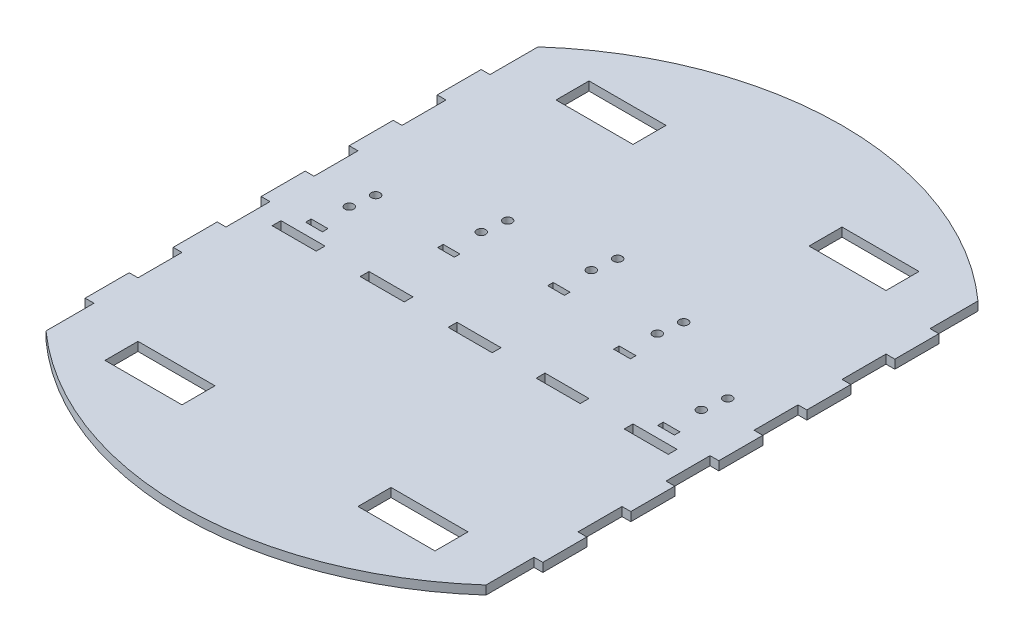
SolidWorks part; units mm, degrees
ref_plane "Přední rovina" through (0, 0, 0) normal (0, 0, 1) x (1, 0, 0)
ref_plane "Horní rovina" through (0, 0, 0) normal (0, 1, 0) x (1, 0, 0)
ref_plane "Pravá rovina" through (0, 0, 0) normal (1, 0, 0) x (0, 0, -1)
sketch "Skica1" plane through (0, 0, 0) normal (0, 1, 0) x (1, 0, 0)
  line L0 (-150, 0) -> (150, 0)
  line L5 (-200, 111.8034) -> (-100, 111.8034)
  line L6 (-200, 111.8034) -> (-200, -111.8034)
  line L7 (-200, -111.8034) -> (-100, -111.8034)
  line L8 (-100, 111.8034) -> (-100, -111.8034)
  line L9 (-200, 111.8034) -> (-100, -111.8034) construction
  line L10 (-200, -111.8034) -> (-100, 111.8034) construction
  line L15 (200, -111.8034) -> (100, -111.8034)
  line L16 (100, 111.8034) -> (100, -111.8034)
  line L17 (-100, -90) -> (-104, -90)
  line L18 (-100, -90) -> (-100, -70)
  line L19 (-100, -70) -> (-104, -70)
  line L20 (-104, -90) -> (-104, -70)
  line L21 (-100, -50) -> (-104, -50)
  line L22 (-100, -50) -> (-100, -30)
  line L23 (-100, -30) -> (-104, -30)
  line L24 (-104, -50) -> (-104, -30)
  line L25 (0, -150) -> (0, 150)
  line L26 (-100, 30) -> (-104, 30)
  line L27 (-104, 50) -> (-104, 30)
  line L28 (-100, 50) -> (-104, 50)
  line L29 (-100, 50) -> (-100, 30)
  line L30 (-100, 70) -> (-104, 70)
  line L31 (-104, 90) -> (-104, 70)
  line L32 (-100, 90) -> (-104, 90)
  line L33 (-100, 90) -> (-100, 70)
  line L34 (200, 111.8034) -> (100, 111.8034)
  line L35 (200, 111.8034) -> (200, -111.8034)
  line L36 (100, 90) -> (100, 70)
  line L37 (100, 90) -> (104, 90)
  line L38 (104, 90) -> (104, 70)
  line L39 (100, 70) -> (104, 70)
  line L40 (100, 50) -> (100, 30)
  line L41 (100, 50) -> (104, 50)
  line L42 (104, 50) -> (104, 30)
  line L43 (100, 30) -> (104, 30)
  line L44 (100, -30) -> (104, -30)
  line L45 (104, -50) -> (104, -30)
  line L46 (100, -50) -> (104, -50)
  line L47 (100, -50) -> (100, -30)
  line L48 (100, -70) -> (104, -70)
  line L49 (104, -90) -> (104, -70)
  line L50 (100, -90) -> (104, -90)
  line L51 (100, -90) -> (100, -70)
  line L52 (-3.81, 22.54) -> (3.81, 22.54)
  line L53 (-83.81, -10) -> (-76.19, -10)
  line L54 (-83.81, -10) -> (-83.81, -7.46)
  line L55 (-83.81, -7.46) -> (-76.19, -7.46)
  line L56 (-76.19, -10) -> (-76.19, -7.46)
  line L57 (-3.81, 22.54) -> (-3.81, 20)
  line L58 (-3.81, 20) -> (3.81, 20)
  line L59 (3.81, 22.54) -> (3.81, 20)
  line L60 (-43.81, 10) -> (-36.19, 10)
  line L61 (-43.81, 10) -> (-43.81, 12.54)
  line L62 (-43.81, 12.54) -> (-36.19, 12.54)
  line L63 (-36.19, 10) -> (-36.19, 12.54)
  line L64 (43.81, 10) -> (43.81, 12.54)
  line L65 (43.81, 12.54) -> (36.19, 12.54)
  line L66 (36.19, 10) -> (36.19, 12.54)
  line L67 (43.81, 10) -> (36.19, 10)
  line L68 (83.81, -7.46) -> (76.19, -7.46)
  line L69 (76.19, -10) -> (76.19, -7.46)
  line L70 (83.81, -10) -> (76.19, -10)
  line L71 (83.81, -10) -> (83.81, -7.46)
  line L72 (100, 10) -> (104, 10)
  line L73 (-100, -10) -> (-104, -10)
  line L74 (-100, -10) -> (-100, 10)
  line L75 (-100, 10) -> (-104, 10)
  line L76 (-104, -10) -> (-104, 10)
  line L77 (104, -10) -> (104, 10)
  line L78 (100, -10) -> (104, -10)
  line L79 (100, -10) -> (100, 10)
  line L80 (-40, 12.54) -> (-40, 26.04)
  line L81 (-80, -7.46) -> (-80, 6.04)
  line L82 (40, 12.54) -> (40, 26.04)
  line L83 (80, -7.46) -> (80, 6.04)
  line L84 (-100, -15) -> (100, -15)
  line L85 (50, -19) -> (30, -19)
  line L86 (-90, -15) -> (-70, -15)
  line L87 (-90, -15) -> (-90, -19)
  line L88 (-90, -19) -> (-70, -19)
  line L89 (-70, -15) -> (-70, -19)
  line L90 (-50, -15) -> (-30, -15)
  line L91 (-50, -15) -> (-50, -19)
  line L92 (-50, -19) -> (-30, -19)
  line L93 (-30, -15) -> (-30, -19)
  line L94 (-10, -15) -> (10, -15)
  line L95 (-10, -15) -> (-10, -19)
  line L96 (-10, -19) -> (10, -19)
  line L97 (10, -15) -> (10, -19)
  line L98 (30, -15) -> (30, -19)
  line L99 (50, -15) -> (30, -15)
  line L100 (50, -15) -> (50, -19)
  line L101 (90, -19) -> (70, -19)
  line L102 (70, -15) -> (70, -19)
  line L103 (90, -15) -> (70, -15)
  line L104 (90, -15) -> (90, -19)
  line L105 (75, -95) -> (40, -95)
  line L106 (40, -110) -> (40, -95)
  line L107 (-75, -110) -> (-40, -110)
  line L108 (-75, -110) -> (-75, -95)
  line L109 (-75, -95) -> (-40, -95)
  line L110 (-40, -110) -> (-40, -95)
  line L111 (75, -110) -> (40, -110)
  line L112 (75, -110) -> (75, -95)
  line L113 (-75, 95) -> (-40, 95)
  line L114 (-40, 110) -> (-40, 95)
  line L115 (-75, 110) -> (-40, 110)
  line L116 (-75, 110) -> (-75, 95)
  line L117 (75, 110) -> (75, 95)
  line L118 (75, 110) -> (40, 110)
  line L119 (40, 110) -> (40, 95)
  line L120 (75, 95) -> (40, 95)
  circle A0 centre (0, 0) radius 150
  circle A1 centre (0, 36.04) radius 2
  circle A2 centre (1.5, 46.54) radius 2
  circle A3 centre (80, 6.04) radius 2
  circle A4 centre (40, 26.04) radius 2
  circle A5 centre (41.5, 36.54) radius 2
  circle A6 centre (81.5, 16.54) radius 2
  circle A7 centre (-40, 26.04) radius 2
  circle A8 centre (-38.5, 36.54) radius 2
  circle A9 centre (-80, 6.04) radius 2
  circle A10 centre (-78.5, 16.54) radius 2
  point P2 (-150, 0)
  point P8 (150, 0)
  point P17 (-102, -90)
  point P50 (-76.19, -8.73)
  point P64 (-80, -7.46)
  point P71 (-40, 12.54)
  dimension "D1" = 300
  dimension "D26" = 4
  dimension "D28" = 4
  dimension "D31" = 4
  dimension "D32" = 4
  dimension "D35" = 4
  dimension "D36" = 4
  dimension "D37" = 4
  dimension "D38" = 4
  dimension "D39" = 4
  dimension "D40" = 4
  dimension "D3" = 4
  dimension "D4" = 20
  dimension "D5" = 20
  dimension "D6" = 4
  dimension "D7" = 20
  dimension "D8" = 30
  dimension "D9" = 2.54
  dimension "D10" = 7.62
  dimension "D11" = 7.62
  dimension "D12" = 2.54
  dimension "D13" = 3.81
  dimension "D14" = 80
  dimension "D15" = 7.62
  dimension "D16" = 2.54
  dimension "D17" = 40
  dimension "D18" = 20
  dimension "D19" = 10
  dimension "D20" = 10
  dimension "D21" = 10
  dimension "D22" = 20
  dimension "D23" = 4
  dimension "D24" = 50
  dimension "D25" = 90
  dimension "D27" = 13.5
  dimension "D29" = 24
  dimension "D30" = 1.5
  dimension "D33" = 13.5
  dimension "D34" = 13.5
  dimension "D41" = 1.5
  dimension "D42" = 24
  dimension "D43" = 1.5
  dimension "D44" = 24
  dimension "D45" = 13.5
  dimension "D46" = 13.5
  dimension "D47" = 1.5
  dimension "D48" = 24
  dimension "D49" = 24
  dimension "D50" = 1.5
  dimension "D51" = 200
  dimension "D52" = 15
  dimension "D53" = 20
  dimension "D54" = 20
  dimension "D55" = 20
  dimension "D56" = 10
  dimension "D57" = 20
  dimension "D58" = 20
  dimension "D59" = 4
  dimension "D60" = 15
  dimension "D61" = 35
  dimension "D62" = 25
  dimension "D63" = 95
extrude "Přidat vysunutím1" add sketch "Skica1" along normal blind 4 contours L8 A0 L25 L96 L95 L84 L93 L92 L91 L89 L88 L87 | L25 A0 L16 L84 L104 L101 L102 L100 L85 L98 L97 L96 | A3 L0 L16 A0 L25 A2 A1 L52 L59 L58 A6 A5 A4 L65 L64 L67 L66 | A9 L0 L25 L58 L57 L52 A1 A2 A0 L8 A10 A8 A7 L62 L63 L60 L61 | L25 L84 L16 L0 L68 L71 L70 L69 | L8 L84 L25 L0 L55 L56 L53 L54 | L8 L32 L31 L30 | L76 L73 L8 L0 | L76 L0 L8 L75 | L20 L17 L8 L19 | L27 L26 L29 L28 | L24 L23 L22 L21 | L38 L39 L36 L37 | L42 L43 L40 L41 | L77 L72 L79 L78 | L45 L44 L47 L46 | L49 L48 L51 L50 region at (-102, 0, -5) region at (-102, 0, 5) region at (-47.4054, 0, -68.4524) region at (-47.0137, 0, 76.8813) region at (-49.6078, 0, 7.4839) region at (-102, 0, -80) region at (47.437, 0, -68.4703) region at (-102, 0, 80) region at (47.0137, 0, 76.8813) region at (49.6078, 0, 7.4839)
